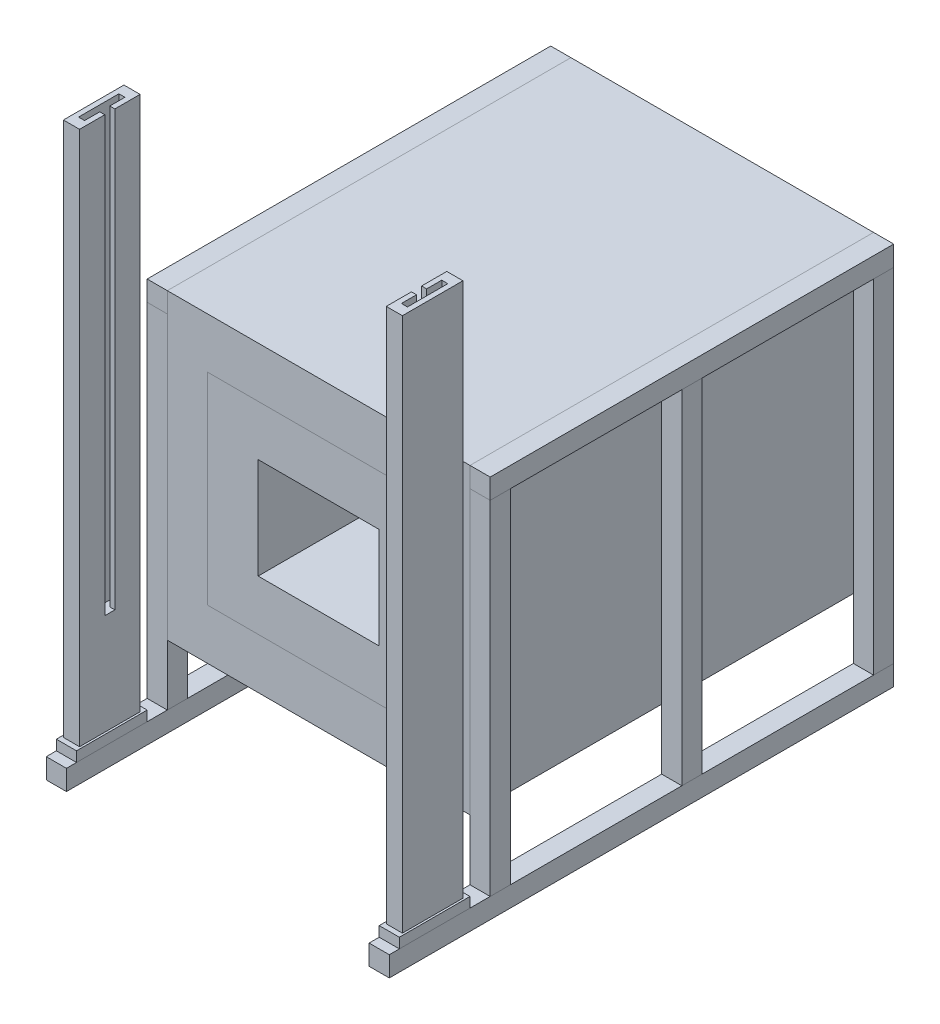
SolidWorks part; units mm, degrees
ref_plane "Спереди" through (0, 0, 0) normal (0, 0, 1) x (1, 0, 0)
ref_plane "Сверху" through (0, 0, 0) normal (0, 1, 0) x (1, 0, 0)
ref_plane "Справа" through (0, 0, 0) normal (1, 0, 0) x (0, 0, -1)
sketch "Эскиз1" plane through (0, 0, 0) normal (0, 0, 1) x (1, 0, 0)
  line L1 (-300, 250) -> (300, 250)
  line L2 (-300, 250) -> (-300, -250)
  line L3 (-300, -250) -> (300, -250)
  line L4 (300, 250) -> (300, -250)
  line L5 (-550, 500) -> (550, 500)
  line L6 (-550, 500) -> (-550, -500)
  line L7 (-550, -500) -> (550, -500)
  line L8 (550, 500) -> (550, -500)
  point P8 (0, 250)
  point P10 (300, 0)
  dimension "D1" = 600
  dimension "D2" = 500
  dimension "D3" = 250
  dimension "D4" = 250
  dimension "D5" = 250
  dimension "D6" = 250
extrude "Бобышка-Вытянуть1" add sketch "Эскиз1" against normal blind 1300
sketch "Эскиз2" plane through (0, -250, 0) normal (0, 1, 0) x (1, 0, 0)
  line L0 (300, 1300) -> (300, 0) construction
  line L1 (-300, 1300) -> (300, 1300)
  line L2 (-300, 1300) -> (-300, 1200)
  line L3 (-300, 1200) -> (300, 1200)
  line L4 (300, 1300) -> (300, 1200)
  dimension "D1" = 100
extrude "Бобышка-Вытянуть2" add sketch "Эскиз2" along normal up to surface (500 mm away) up to face at (0, 250, -650)
sketch "Эскиз3" plane through (0, 0, 0) normal (0, 0, 1) x (1, 0, 0)
  line L0 (550, -500) -> (550, 500) construction
  line L1 (-550, -500) -> (550, -500) construction
  line L2 (-550, 500) -> (-550, -500) construction
  line L3 (550, 500) -> (-550, 500) construction
  line L4 (550, -500) -> (550, 500)
  line L5 (-550, -500) -> (550, -500)
  line L6 (-550, 500) -> (-550, -500)
  line L7 (550, 500) -> (-550, 500)
  line L9 (750, 750) -> (-750, 750)
  line L10 (750, 750) -> (750, -750)
  line L11 (750, -750) -> (-750, -750)
  line L12 (-750, 750) -> (-750, -750)
  point P8 (-655.9624, -626.1459)
  point P9 (750, 0)
  point P11 (0, -750)
  dimension "D1" = 1500
  dimension "D2" = 1500
extrude "Бобышка-Вытянуть3" add sketch "Эскиз3" against normal blind 2000 separate body
sketch "Эскиз4" plane through (0, -500, 0) normal (0, 1, 0) x (1, 0, 0)
  line L0 (550, 2000) -> (550, 0) construction
  line L1 (-550, 2000) -> (550, 2000)
  line L2 (-550, 2000) -> (-550, 1900)
  line L3 (-550, 1900) -> (550, 1900)
  line L4 (550, 2000) -> (550, 1900)
  dimension "D1" = 100
extrude "Бобышка-Вытянуть4" add sketch "Эскиз4" along normal up to surface (1000 mm away) up to face at (0, 500, -1000)
sketch "Эскиз7" plane through (0, 0, 0) normal (0, 0, 1) x (1, 0, 0)
  line L1 (-750, 750) -> (-850, 750)
  line L2 (-750, 750) -> (-750, 650)
  line L3 (-750, 650) -> (-850, 650)
  line L4 (-850, 750) -> (-850, 650)
  line L5 (-750, -1150) -> (-850, -1150)
  line L6 (-750, -1150) -> (-750, -1050)
  line L7 (-750, -1050) -> (-850, -1050)
  line L8 (-850, -1150) -> (-850, -1050)
  line L9 (750, -1150) -> (850, -1150)
  line L10 (750, -1150) -> (750, -1050)
  line L11 (750, -1050) -> (850, -1050)
  line L12 (850, -1150) -> (850, -1050)
  line L13 (750, 750) -> (850, 750)
  line L14 (750, 750) -> (750, 650)
  line L15 (750, 650) -> (850, 650)
  line L16 (850, 750) -> (850, 650)
  dimension "D1" = 100
  dimension "D2" = 1900
extrude "Бобышка-Вытянуть7" add sketch "Эскиз7" against normal up to surface (2000 mm away) separate body up to face at (0, 0, -2000)
extrude "Бобышка-Вытянуть8" add sketch "Эскиз7<2>" along normal blind 500 contours L8 L5 L6 L7 | L9 L12 L11 L10 region at (-800, -1100, 0) region at (800, -1100, 0)
sketch "Эскиз7<2>" plane through (0, 0, 0) normal (0, 0, 1) x (1, 0, 0) same geometry as "Эскиз7"
sketch "Эскиз8" plane through (0, 650, 0) normal (0, -1, 0) x (1, 0, 0)
  line L0 (850, -2000) -> (850, 0) construction
  line L1 (850, 0) -> (750, 0)
  line L2 (850, 0) -> (850, -100)
  line L3 (850, -100) -> (750, -100)
  line L4 (750, 0) -> (750, -100)
  line L5 (750, 0) -> (850, 0) construction
  line L6 (750, -2000) -> (750, 0) construction
  line L7 (850, -2000) -> (750, -2000)
  line L8 (850, -2000) -> (850, -1900)
  line L9 (850, -1900) -> (750, -1900)
  line L10 (750, -2000) -> (750, -1900)
  line L11 (0, 0) -> (0, -1237.1824) construction
  line L12 (850, -950) -> (750, -950)
  line L13 (850, -950) -> (850, -1050)
  line L14 (850, -1050) -> (750, -1050)
  line L15 (750, -950) -> (750, -1050)
  line L16 (-750, -950) -> (-750, -1050)
  line L17 (-850, -1050) -> (-750, -1050)
  line L18 (-850, -950) -> (-850, -1050)
  line L19 (-850, -950) -> (-750, -950)
  line L20 (-750, -2000) -> (-750, -1900)
  line L21 (-850, -1900) -> (-750, -1900)
  line L22 (-850, -2000) -> (-850, -1900)
  line L23 (-850, -2000) -> (-750, -2000)
  line L24 (-750, 0) -> (-750, -100)
  line L25 (-850, -100) -> (-750, -100)
  line L26 (-850, 0) -> (-850, -100)
  line L27 (-850, 0) -> (-750, 0)
  point P19 (850, -1000)
  dimension "D1" = 100
  dimension "D2" = 1000
extrude "Бобышка-Вытянуть9" add sketch "Эскиз8" along normal up to surface (1700 mm away) separate body up to face at (800, -1050, -750)
sketch "Эскиз9" plane through (0, -1050, 0) normal (0, 1, 0) x (1, 0, 0)
  line L0 (750, 2000) -> (750, -500) construction
  line L1 (750, -450) -> (850, -450)
  line L2 (750, -450) -> (750, -100)
  line L3 (750, -100) -> (850, -100)
  line L4 (850, -450) -> (850, -100)
  line L5 (850, 2000) -> (850, -500) construction
  line L6 (750, -500) -> (850, -500) construction
  line L7 (750, 0) -> (850, 0) construction
  line L8 (760, -125) -> (840, -125)
  line L9 (840, -125) -> (840, -425)
  line L10 (840, -425) -> (760, -425)
  line L11 (760, -425) -> (760, -300)
  line L12 (760, -300) -> (785, -300)
  line L13 (785, -300) -> (785, -375)
  line L14 (785, -375) -> (815, -375)
  line L15 (815, -375) -> (815, -175)
  line L16 (815, -175) -> (785, -175)
  line L17 (785, -175) -> (785, -250)
  line L18 (785, -250) -> (760, -250)
  line L19 (760, -250) -> (760, -125)
  line L20 (0, 0) -> (0, -750.0295) construction
  line L21 (-760, -250) -> (-760, -125)
  line L22 (-785, -250) -> (-760, -250)
  line L23 (-785, -175) -> (-785, -250)
  line L24 (-815, -175) -> (-785, -175)
  line L25 (-815, -375) -> (-815, -175)
  line L26 (-785, -375) -> (-815, -375)
  line L27 (-785, -300) -> (-785, -375)
  line L28 (-760, -300) -> (-785, -300)
  line L29 (-760, -425) -> (-760, -300)
  line L30 (-840, -425) -> (-760, -425)
  line L31 (-840, -125) -> (-840, -425)
  line L32 (-760, -125) -> (-840, -125)
  line L33 (-850, -450) -> (-850, -100)
  line L34 (-750, -100) -> (-850, -100)
  line L35 (-750, -450) -> (-750, -100)
  line L36 (-750, -450) -> (-850, -450)
  point P22 (800, -175)
  dimension "D1" = 50
  dimension "D2" = 100
  dimension "D3" = 10
  dimension "D4" = 10
  dimension "D5" = 25
  dimension "D6" = 25
  dimension "D7" = 25
  dimension "D8" = 25
  dimension "D9" = 50
  dimension "D10" = 125
extrude "Бобышка-Вытянуть10" add sketch "Эскиз9" along normal blind 50 separate body
extrude "Бобышка-Вытянуть11" add sketch "Эскиз9<2>" along normal blind 2700 contours L19 L18 L17 L16 L15 L14 L13 L12 L11 L10 L9 L8 | L21 L32 L31 L30 L29 L28 L27 L26 L25 L24 L23 L22 region at (800, -1050, 128.1048) region at (-772.5, -1050, 246.8952)
sketch "Эскиз9<2>" plane through (0, -1050, 0) normal (0, 1, 0) x (1, 0, 0) same geometry as "Эскиз9"
sketch "Эскиз10" plane through (0, -1000, 0) normal (0, 1, 0) x (1, 0, 0)
  line L0 (815, -175) -> (785, -175) construction
  line L1 (815, -175) -> (785, -175)
  line L2 (815, -175) -> (815, -375)
  line L3 (815, -375) -> (785, -375)
  line L4 (785, -175) -> (785, -375)
  line L5 (785, -175) -> (815, -175) construction
  line L6 (785, -300) -> (760, -300) construction
  line L7 (760, -250) -> (785, -250)
  line L12 (760, -250) -> (760, -300)
  line L13 (760, -300) -> (785, -300)
  line L14 (785, -250) -> (785, -300)
  line L15 (815, -375) -> (815, -175) construction
  line L16 (0, 0) -> (0, -566.7234) construction
  line L17 (750, 0) -> (-750, 0) construction
  line L18 (-785, -250) -> (-785, -300)
  line L19 (-760, -300) -> (-785, -300)
  line L20 (-760, -250) -> (-760, -300)
  line L21 (-760, -250) -> (-785, -250)
  line L22 (-785, -175) -> (-785, -375)
  line L23 (-815, -375) -> (-785, -375)
  line L24 (-815, -175) -> (-815, -375)
  line L25 (-815, -175) -> (-785, -175)
  line M18 (760, -300) -> (785, -300)
  line M24 (785, -250) -> (760, -250)
extrude "Бобышка-Вытянуть12" add sketch "Эскиз10" along normal blind 500 contours L12 L4 M24 M18 | L25 L24 L23 L22 L18 | L20 L21 L18 L19 | L2 L3 L4 L1 region at (772.5, -1000, 275) region at (-772.5, -1000, 275) region at (-800, -1000, 275)
